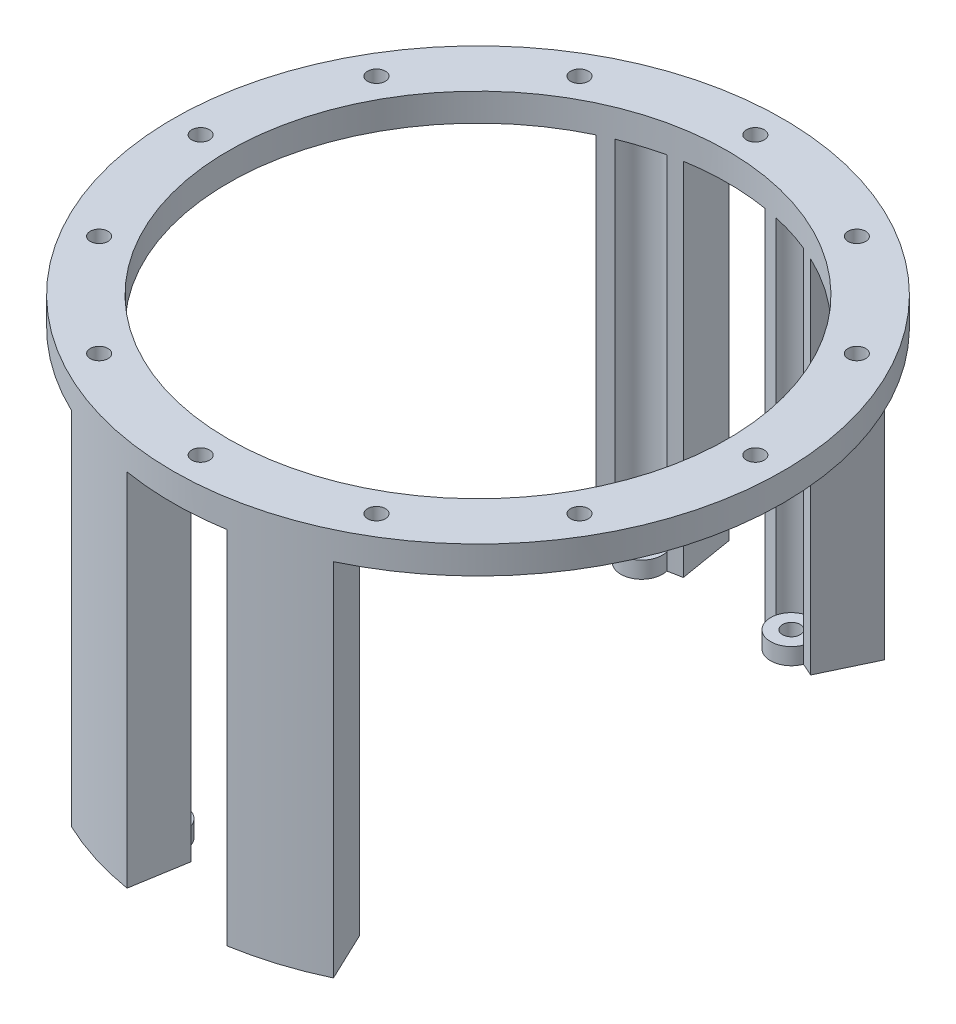
SolidWorks part; units mm, degrees
ref_plane "Front Plane" through (0, 0, 0) normal (0, 0, 1) x (1, 0, 0)
ref_plane "Top Plane" through (0, 0, 0) normal (0, 1, 0) x (1, 0, 0)
ref_plane "Right Plane" through (0, 0, 0) normal (1, 0, 0) x (0, 0, -1)
sketch "Sketch1" plane through (0, 0, 0) normal (0, 1, 0) x (1, 0, 0)
  line L0 (0, 72.9046) -> (0, -73.3838) construction
  line L1 (-13.5, -43) -> (13.5, -43)
  line L2 (-13.5, -43) -> (-13.5, 43) construction
  line L3 (-13.5, 43) -> (13.5, 43) construction
  line L4 (13.5, -43) -> (13.5, 43) construction
  line L5 (-13.5, -43) -> (13.5, 43) construction
  line L6 (-13.5, 43) -> (13.5, -43) construction
  line L7 (0, 0) -> (13.5, 43) construction
  line L8 (0, 0) -> (12.9164, 77.7703) construction
  line L9 (0, 0) -> (35.3935, 74.4383) construction
  line L10 (7.3728, 44.3919) -> (9.0112, 54.2568)
  line L11 (19.3233, 40.64) -> (23.6173, 49.6711)
  line L12 (-19.3233, 40.64) -> (-23.6173, 49.6711)
  line L13 (-7.3728, 44.3919) -> (-9.0112, 54.2568)
  line L14 (-44.2819, 0) -> (58.5874, 0) construction
  line L15 (-13.5, -43) -> (13.5, -43) construction
  line L16 (-7.3728, -44.3919) -> (-9.0112, -54.2568)
  line L17 (-19.3233, -40.64) -> (-23.6173, -49.6711)
  line L18 (19.3233, -40.64) -> (23.6173, -49.6711)
  line L19 (7.3728, -44.3919) -> (9.0112, -54.2568)
  circle A2 centre (13.5, 43) radius 1.6
  circle A3 centre (13.5, 43) radius 3.75
  arc A6 (7.3728, 44.3919) -> (9.8611, 43.9062) centre (0, 0) cw
  arc A7 (19.3233, 40.64) -> (17.0039, 41.6638) centre (0, 0) ccw
  arc A8 (9.0112, 54.2568) -> (23.6173, 49.6711) centre (0, 0) cw
  arc A9 (-19.3233, 40.64) -> (-17.0039, 41.6638) centre (0, 0) cw
  circle A10 centre (-13.5, 43) radius 1.6
  circle A11 centre (-13.5, 43) radius 3.75
  arc A12 (-7.3728, 44.3919) -> (-9.8611, 43.9062) centre (0, 0) ccw
  arc A13 (-9.0112, 54.2568) -> (-23.6173, 49.6711) centre (0, 0) ccw
  arc A14 (-9.0112, -54.2568) -> (-23.6173, -49.6711) centre (0, 0) cw
  arc A15 (-7.3728, -44.3919) -> (-9.8611, -43.9062) centre (0, 0) cw
  circle A16 centre (-13.5, -43) radius 3.75
  circle A17 centre (-13.5, -43) radius 1.6
  arc A18 (-19.3233, -40.64) -> (-17.0039, -41.6638) centre (0, 0) ccw
  arc A19 (9.0112, -54.2568) -> (23.6173, -49.6711) centre (0, 0) ccw
  arc A20 (19.3233, -40.64) -> (17.0039, -41.6638) centre (0, 0) cw
  arc A21 (7.3728, -44.3919) -> (9.8611, -43.9062) centre (0, 0) ccw
  circle A22 centre (13.5, -43) radius 3.75
  circle A23 centre (13.5, -43) radius 1.6
  arc A24 (-19.3233, -40.64) -> (-19.3233, 40.64) centre (0, 0) cw
  arc A25 (-7.3728, 44.3919) -> (7.3728, 44.3919) centre (0, 0) cw
  arc A26 (7.3728, -44.3919) -> (-7.3728, -44.3919) centre (0, 0) cw
  arc A27 (-23.6173, 49.6711) -> (-23.6173, -49.6711) centre (0, 0) ccw
  arc A28 (-9.0112, 54.2568) -> (9.0112, 54.2568) centre (0, 0) cw
  arc A29 (-9.0112, -54.2568) -> (9.0112, -54.2568) centre (0, 0) ccw
  arc A30 (19.3233, -40.64) -> (19.3233, 40.64) centre (0, 0) ccw
  arc A31 (23.6173, 49.6711) -> (23.6173, -49.6711) centre (0, 0) cw
  point P0 (0, 0)
  dimension "D3" = 3.2
  dimension "D4" = 7.5
  dimension "D5" = 45
  dimension "D6" = 45
  dimension "D9" = 55
  dimension "D1" = 86
  dimension "D2" = 27
  dimension "D7" = 8
  dimension "D8" = 8
extrude "Boss-Extrude3" add sketch "Sketch1" along normal blind 3 contours A23 A22 | A17 A16 | A3 A2 | A11 A10 region at (-9.8832, 0, 43.4436) region at (12.8399, 0, 39.4164) region at (-14.5915, 0, -46.4766) region at (12.4085, 0, -39.5234)
extrude "Boss-Extrude4" add sketch "Sketch1<7>" along normal blind 65 contours A20 A22 A21 L19 A19 L18 | A18 L17 A14 L16 A15 A16 | A8 L10 A6 A3 A7 L11 | L13 A13 L12 A9 A11 A12 region at (-15.1794, 0, 48.3492) region at (15.1794, 0, 48.3492) region at (-15.1794, 0, -48.3492) region at (15.1794, 0, -48.3492)
sketch "Sketch1<7>" plane through (0, 0, 0) normal (0, 1, 0) x (1, 0, 0) same geometry as "Sketch1"
sketch "Sketch3" plane through (0, 65, 0) normal (0, 1, 0) x (1, 0, 0)
  line L0 (0, 164.6614) -> (0, -64.6614) construction
  circle A0 centre (0, 0) radius 45
  circle A1 centre (0, 0) radius 55
  circle A2 centre (0, 50) radius 1.6
  circle A3 centre (25, 43.3013) radius 1.6
  circle A4 centre (43.3013, 25) radius 1.6
  circle A5 centre (50, 0) radius 1.6
  circle A6 centre (43.3013, -25) radius 1.6
  circle A7 centre (25, -43.3013) radius 1.6
  circle A8 centre (0, -50) radius 1.6
  circle A9 centre (-25, -43.3013) radius 1.6
  circle A10 centre (-43.3013, -25) radius 1.6
  circle A11 centre (-50, 0) radius 1.6
  circle A12 centre (-43.3013, 25) radius 1.6
  circle A13 centre (-25, 43.3013) radius 1.6
  point P34 (0, 0)
  dimension "D1" = 3.2
  dimension "D2" = 50
  dimension "D3" = 12
extrude "Boss-Extrude5" add sketch "Sketch3" along normal blind 5
